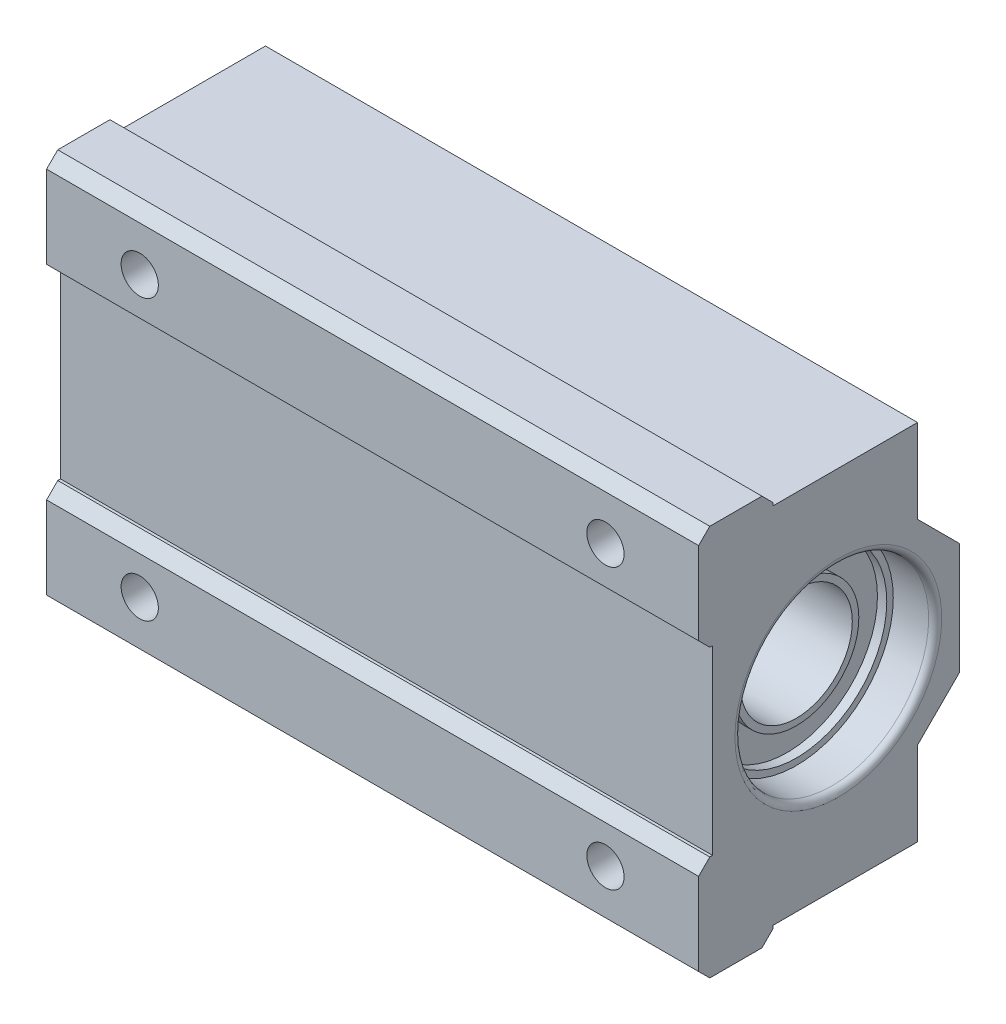
SolidWorks part; units mm, degrees
ref_plane "Alzado" through (0, 0, 0) normal (0, 0, 1) x (1, 0, 0)
ref_plane "Planta" through (0, 0, 0) normal (0, 1, 0) x (1, 0, 0)
ref_plane "Vista lateral" through (0, 0, 0) normal (1, 0, 0) x (0, 0, -1)
sketch "Croquis1" plane through (0, 0, 0) normal (0, 0, 1) x (1, 0, 0)
  line L1 (-35, -21) -> (35, -21)
  line L2 (-35, -21) -> (-35, 21)
  line L3 (-35, 21) -> (35, 21)
  line L4 (35, -21) -> (35, 21)
  line L5 (-35, -21) -> (35, 21) construction
  line L6 (-35, 21) -> (35, -21) construction
  point P0 (0, 0)
  dimension "D1" = 42
  dimension "D2" = 70
extrude "Saliente-Extruir1" add sketch "Croquis1" along normal blind 28
sketch "Croquis2" plane through (35, 0, 0) normal (1, 0, 0) x (0, 0, -1)
  line L0 (-28, 0) -> (0, 0) construction
  line L1 (-28, -21) -> (-28, 21) construction
  line L2 (-28, 9.75) -> (-26.5, 9.75)
  line L3 (-26.5, 9.75) -> (-26.5, -9.75)
  line L4 (-4.5, 21) -> (-4.5, -21) construction
  line L5 (-28, 21) -> (0, 21) construction
  line L6 (-28, -21) -> (0, -21) construction
  line L7 (-28, 19.5) -> (0, 19.5) construction
  line L8 (0, -21) -> (0, 21) construction
  line L9 (-20, 21) -> (-20, -21) construction
  line L10 (-20, 19.5) -> (-4.5, 19.5)
  line L11 (-20, 21) -> (-20, 19.5)
  line L12 (0, -6) -> (0, 6)
  line L13 (0, 6) -> (-4.5, 10.5)
  line L14 (-4.5, 10.5) -> (-4.5, 19.5)
  line L15 (0, -6) -> (-4.5, -10.5)
  line L16 (-4.5, -10.5) -> (-4.5, -19.5)
  line L17 (-20, -19.5) -> (-4.5, -19.5)
  line L18 (-20, -21) -> (-20, -19.5)
  line L19 (-28, -9.75) -> (-26.5, -9.75)
  line L20 (-28, -21) -> (0, -21)
  line L21 (-28, 21) -> (0, 21)
  line L22 (-28, -21) -> (-28, 21)
  line L23 (0, -6) -> (0, -21)
  line L24 (0, 6) -> (0, 21)
  point P30 (-26.5, 0)
  line M12 (0, -21) -> (0, 21)
  line M13 (0, 21) -> (-28, 21)
  line M14 (-28, 21) -> (-28, -21)
  line M15 (-28, -21) -> (0, -21)
  dimension "D6" = 6
  dimension "D1" = 1.5
  dimension "D2" = 9.75
  dimension "D3" = 23.5
  dimension "D4" = 1.5
  dimension "D5" = 8
  dimension "D7" = 45
extrude "Cortar-Extruir1" cut sketch "Croquis2" against normal blind 70 contours L19 L3 L2 M14 | L14 L13 L11 L10 M12 M13 | L18 L15 L16 L17 M15 M12 region at (35, 0, 27.25) region at (35, 20.75, 10) region at (35, -20.25, 19.75)
sketch "Croquis3" plane through (0, 0, 28) normal (0, 0, 1) x (1, 0, 0)
  line L1 (25, 15) -> (-25, 15) construction
  line L2 (25, 15) -> (25, -15) construction
  line L3 (25, -15) -> (-25, -15) construction
  line L4 (-25, 15) -> (-25, -15) construction
  line L5 (25, 15) -> (-25, -15) construction
  line L6 (25, -15) -> (-25, 15) construction
  circle A0 centre (25, -15) radius 2
  circle A1 centre (-25, -15) radius 2
  circle A2 centre (-25, 15) radius 2
  circle A3 centre (25, 15) radius 2
  point P0 (0, 0)
  dimension "D3" = 4
  dimension "D1" = 50
  dimension "D2" = 30
extrude "Cortar-Extruir2" cut sketch "Croquis3" against normal blind 70
sketch "Croquis4" plane through (35, 0, 0) normal (1, 0, 0) x (0, 0, -1)
  line L0 (-26.5, 0) -> (0, 0) construction
  line L1 (-26.5, 9.75) -> (-26.5, -9.75) construction
  line L2 (0, -6) -> (0, 6) construction
  circle A0 centre (-13, 0) radius 6
  dimension "D1" = 13
  dimension "D2" = 12
extrude "Cortar-Extruir3" cut sketch "Croquis4" against normal blind 70
sketch "Croquis5" plane through (35, 0, 0) normal (1, 0, 0) x (0, 0, -1)
  circle A0 centre (-13, 0) radius 10.4
  dimension "D1" = 20.8
extrude "Cortar-Extruir4" cut sketch "Croquis5" against normal blind 4.5
sketch "Croquis6" plane through (30.5, 0, 0) normal (1, 0, 0) x (0, 0, -1)
  circle A2 centre (-13, 0) radius 6.7
  circle A3 centre (-13, 0) radius 6.7
  circle A5 centre (-13, 0) radius 9.7
  circle A6 centre (-13, 0) radius 9.7
  dimension "D1" = 0.7
  dimension "D2" = 0.7
extrude "Cortar-Extruir5" cut sketch "Croquis6" against normal blind 1
mirror "Simetría1" about plane through (0, 0, 0) normal (1, 0, 0) of "Cortar-Extruir5", "Cortar-Extruir4"
chamfer "Chaflán1" distance 1.2 angle 45 6 edges at (0, -21, 20) (0, 21, 20) (0, 21, 28) (0, -21, 28) (0, 9.75, 28) (0, -9.75, 28)
fillet "Redondeo1" radius 0.7 2 edges at (35, 0, 2.6) (-35, 0, 2.6)
